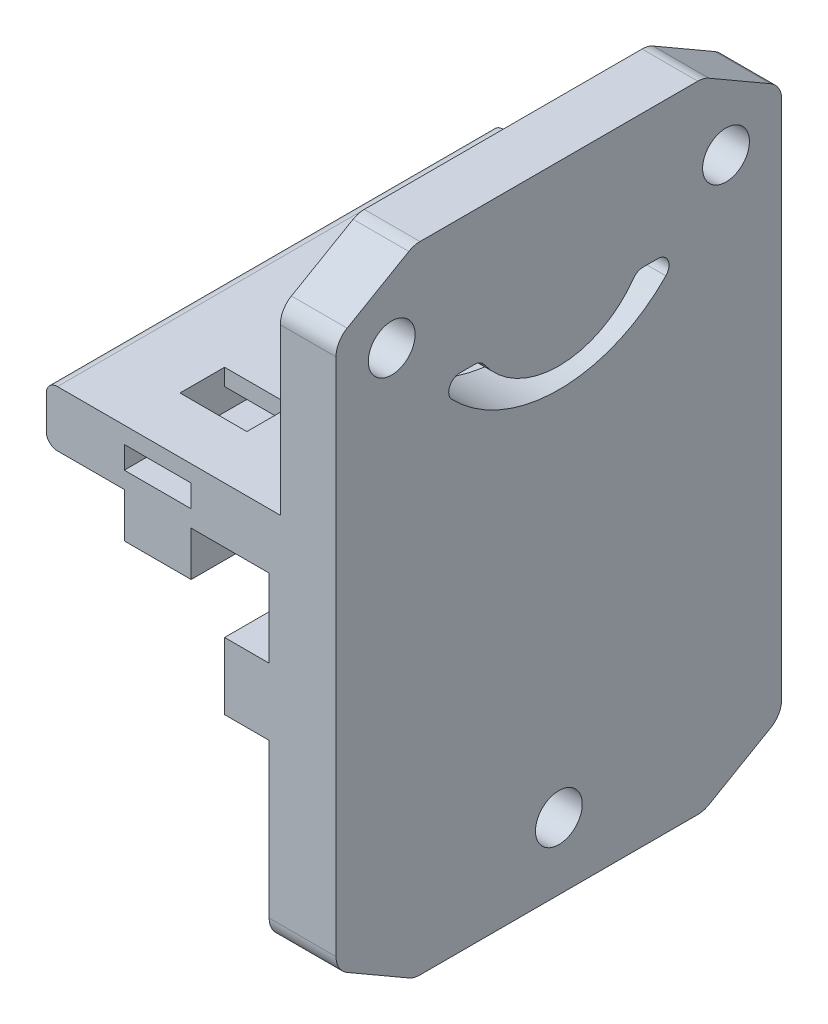
SolidWorks part; units mm, degrees
ref_plane "Plan de face" through (0, 0, 0) normal (0, 0, 1) x (1, 0, 0)
ref_plane "Plan de dessus" through (0, 0, 0) normal (0, 1, 0) x (1, 0, 0)
ref_plane "Plan de droite" through (0, 0, 0) normal (1, 0, 0) x (0, 0, -1)
sketch "Esquisse1" plane through (0, 0, 0) normal (0, 0, 1) x (1, 0, 0)
  line L1 (-13, 25) -> (13, 25)
  line L2 (-13, 25) -> (-13, -25)
  line L3 (-13, -25) -> (13, -25)
  line L4 (13, 25) -> (13, -25)
  dimension "D1" = 26
  dimension "D2" = 50
  dimension "D3" = 13
  dimension "D4" = 25
extrude "Boss.-Extru.1" add sketch "Esquisse1" along normal blind 40
sketch "Esquisse2" plane through (0, 0, 40) normal (0, 0, 1) x (1, 0, 0)
  line L0 (-13, 25) -> (-13, -25) construction
  line L1 (-13, 0) -> (7, 0)
  line L2 (-13, 0) -> (-13, -20)
  line L3 (-13, -20) -> (7, -20)
  line L4 (7, 0) -> (7, -20)
  line L5 (-13, -25) -> (13, -25) construction
  dimension "D1" = 20
  dimension "D2" = 20
  dimension "D3" = 5
extrude "Enlèv. mat.-Extru.1" cut sketch "Esquisse2" against normal through all
sketch "Esquisse3" plane through (0, 0, 40) normal (0, 0, 1) x (1, 0, 0)
  line L0 (7, 0) -> (-13, 0) construction
  line L1 (-6, 0) -> (0, 0)
  line L2 (-6, 0) -> (-6, -4)
  line L3 (-6, -4) -> (0, -4)
  line L4 (0, 0) -> (0, -4)
  line L10 (7, -20) -> (7, 0) construction
  line L11 (7, -7) -> (3, -7)
  line L12 (7, -7) -> (7, -13)
  line L13 (7, -13) -> (3, -13)
  line L14 (3, -7) -> (3, -13)
  line L16 (-13, 25) -> (-13, 0) construction
  dimension "D1" = 4
  dimension "D4" = 7
  dimension "D5" = 6
  dimension "D7" = 6
  dimension "D8" = 4
  dimension "D9" = 7
extrude "Boss.-Extru.2" add sketch "Esquisse3" against normal up to surface (40 mm away) up to face at (-1.5, -5, 0)
sketch "Esquisse7" plane through (0, 0, 40) normal (0, 0, 1) x (1, 0, 0)
  line L0 (13, -25) -> (13, 25) construction
  line L1 (-13, 25) -> (8, 25)
  line L2 (-13, 25) -> (-13, 5)
  line L3 (-13, 5) -> (8, 5)
  line L4 (8, 25) -> (8, 5)
  dimension "D1" = 5
  dimension "D2" = 20
extrude "Enlèv. mat.-Extru.4" cut sketch "Esquisse7" against normal through all
sketch "Esquisse8" plane through (0, 0, 40) normal (0, 0, 1) x (1, 0, 0)
  line L0 (-13, 5) -> (8, 5) construction
  line L1 (-6, 3.5) -> (0, 3.5)
  line L2 (-6, 3.5) -> (-6, 1.5)
  line L3 (-6, 1.5) -> (0, 1.5)
  line L4 (0, 3.5) -> (0, 1.5)
  dimension "D1" = 6
  dimension "D2" = 7
  dimension "D3" = 1.5
  dimension "D4" = 2
extrude "Enlèv. mat.-Extru.5" cut sketch "Esquisse8" against normal through all
sketch "Esquisse9" plane through (0, 5, 0) normal (0, 1, 0) x (1, 0, 0)
  line L0 (-13, 0) -> (8, 0) construction
  line L1 (-6, -31) -> (0, -31)
  line L2 (-6, -31) -> (-6, -35)
  line L3 (-6, -35) -> (0, -35)
  line L4 (0, -31) -> (0, -35)
  line L5 (-6, -5) -> (0, -5)
  line L6 (-6, -5) -> (-6, -9)
  line L7 (-6, -9) -> (0, -9)
  line L8 (0, -5) -> (0, -9)
  line L9 (-13, -40) -> (8, -40) construction
  line L10 (-13, 0) -> (-13, -40) construction
  dimension "D1" = 5
  dimension "D2" = 4
  dimension "D3" = 6
  dimension "D4" = 6
  dimension "D5" = 4
  dimension "D6" = 5
  dimension "D7" = 7
  dimension "D8" = 7
extrude "Enlèv. mat.-Extru.6" cut sketch "Esquisse9" against normal up to surface (3.5 mm away) up to face at (-3, 1.5, 20)
sketch "Esquisse10" plane through (13, 0, 0) normal (1, 0, 0) x (0, 0, -1)
  line L0 (-40, 25) -> (0, 25) construction
  line L1 (-40, -25) -> (-40, 25) construction
  circle A0 centre (-35, 18) radius 2.1
  circle A1 centre (-5, 18) radius 2.1
  dimension "D1" = 4.2
  dimension "D2" = 4.2
  dimension "D3" = 30
  dimension "D4" = 7
  dimension "D5" = 5
  dimension "D6" = 7
extrude "Enlèv. mat.-Extru.7" cut sketch "Esquisse10" against normal through all
sketch "Esquisse12" plane through (8, 0, 0) normal (-1, 0, 0) x (0, 0, 1)
  line L0 (9, 13) -> (13, 13)
  line L1 (27, 13) -> (31, 13)
  line L2 (0, 25) -> (40, 25) construction
  line L3 (0, 5) -> (0, 25) construction
  arc A0 (13, 13) -> (27, 13) centre (20, 17.3268) ccw
  arc A1 (9, 13) -> (31, 13) centre (20, 20.6417) ccw
  dimension "D6" = 8.2293
  dimension "D7" = 13.3939
  dimension "D1" = 4
  dimension "D2" = 4
  dimension "D3" = 12
  dimension "D4" = 14
  dimension "D5" = 9
extrude "Enlèv. mat.-Extru.9" cut sketch "Esquisse12" against normal through all
sketch "Esquisse13" plane through (0, 0, 0) normal (0, 0, -1) x (-1, 0, 0)
  line L1 (-13, -25) -> (13, -25)
  line L2 (-13, -25) -> (-13, -20)
  line L3 (-13, -20) -> (13, -20)
  line L4 (13, -25) -> (13, -20)
extrude "Enlèv. mat.-Extru.10" cut sketch "Esquisse13" against normal through all
fillet "Congé1" radius 1 2 edges at (-13, 5, 20) (-13, 0, 20)
fillet "Congé2" radius 1 4 edges at (10.5, 13, 27) (10.5, 13, 13) (10.5, 13, 31) (10.5, 13, 9)
sketch "Esquisse14" plane through (0, -20, 0) normal (0, -1, 0) x (1, 0, 0)
  line L1 (13, 40) -> (7, 40)
  line L2 (13, 40) -> (13, 0)
  line L3 (13, 0) -> (7, 0)
  line L4 (7, 40) -> (7, 0)
extrude "Boss.-Extru.3" add sketch "Esquisse14" along normal blind 12
chamfer "Chanfrein1" distance 7 angle 30 4 edges at (10.5, 25, 40) (10.5, 25, 0) (10, -32, 40) (10, -32, 0) first distance on face at (10.5, 25, 20) first distance on face at (10, -32, 20)
fillet "Congé3" radius 2 8 edges at (10.5, 20.9585, 0) (10.5, 25, 7) (10.5, 20.9585, 40) (10.5, 25, 33) (10, -27.9585, 0) (10, -32, 7) (10, -32, 33) (10, -27.9585, 40)
sketch "Esquisse16" plane through (13, 0, 0) normal (1, 0, 0) x (0, 0, -1)
  line L0 (-40, -26.8038) -> (-40, 19.8038) construction
  line L1 (-7.5359, -32) -> (-32.4641, -32) construction
  circle A0 centre (-20, -26) radius 2.1
  dimension "D1" = 4.2
  dimension "D2" = 20
  dimension "D3" = 6
extrude "Enlèv. mat.-Extru.11" cut sketch "Esquisse16" against normal through all
